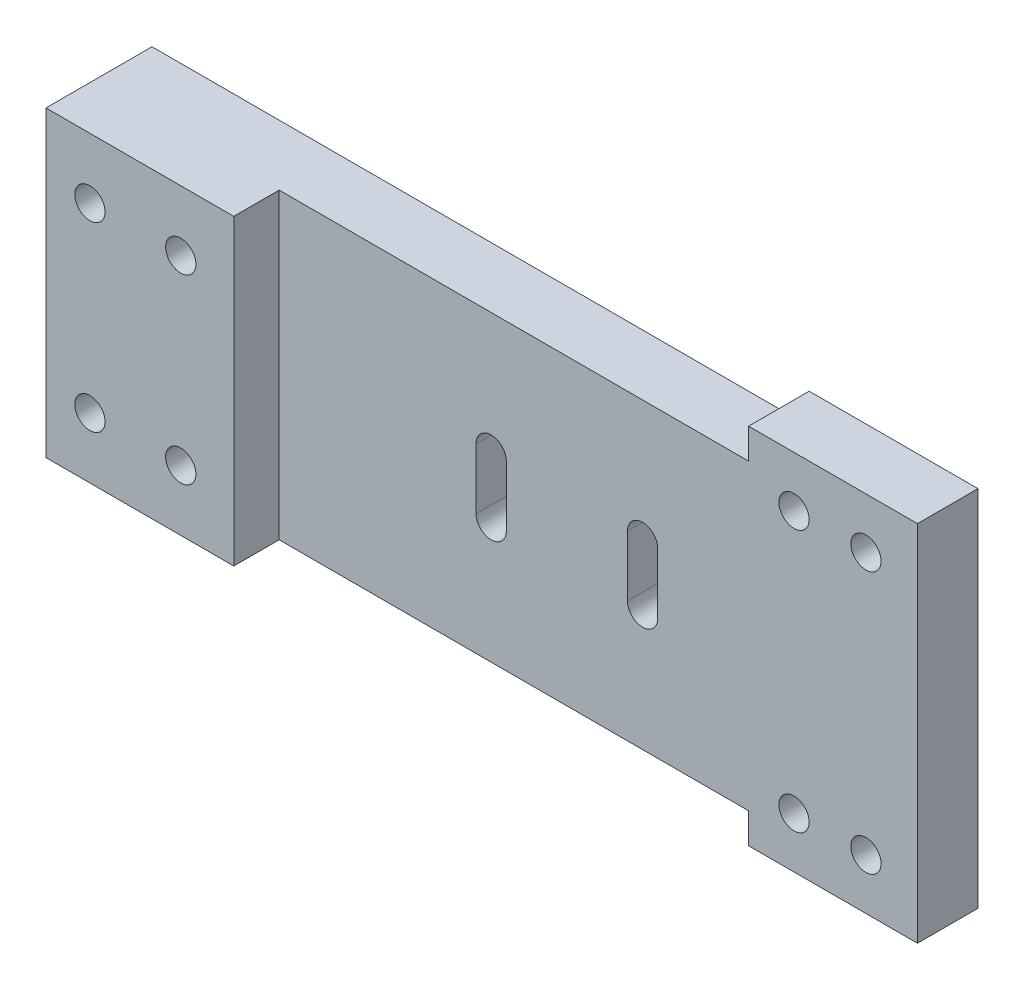
SolidWorks part; units mm, degrees
ref_plane "Front Plane" through (0, 0, 0) normal (0, 0, 1) x (1, 0, 0)
ref_plane "Top Plane" through (0, 0, 0) normal (0, 1, 0) x (1, 0, 0)
ref_plane "Right Plane" through (0, 0, 0) normal (1, 0, 0) x (0, 0, -1)
ref_plane "Plane1" through (0, 0, 246) normal (0, 0, 1) x (1, 0, 0)
sketch "Sketch1" plane through (0, 0, 246) normal (0, 0, 1) x (1, 0, 0)
  line L0 (227.2, 280) -> (336.3, 280)
  line L1 (336.3, 280) -> (336.3, 320)
  line L2 (336.3, 320) -> (227.2, 320)
  line L3 (227.2, 320) -> (227.2, 280)
  line L4 (282, 296) -> (282, 304)
  line L5 (278, 304) -> (278, 296)
  line L6 (302, 296) -> (302, 304)
  line L7 (298, 304) -> (298, 296)
  arc A0 (282, 304) -> (278, 304) centre (280, 304) ccw
  arc A1 (278, 296) -> (282, 296) centre (280, 296) ccw
  arc A2 (302, 304) -> (298, 304) centre (300, 304) ccw
  arc A3 (298, 296) -> (302, 296) centre (300, 296) ccw
extrude "Boss-Extrude1" add sketch "Sketch1" along normal blind 8
sketch "Sketch2" plane through (0, 0, 246) normal (0, 0, 1) x (1, 0, 0)
  line L0 (314, 276) -> (336.3, 276)
  line L1 (336.3, 276) -> (336.3, 324)
  line L2 (336.3, 324) -> (314, 324)
  line L3 (314, 324) -> (314, 276)
extrude "Boss-Extrude2" add sketch "Sketch2" along normal blind 8
ref_plane "Plane2" through (0, 0, 254) normal (0, 0, 1) x (1, 0, 0)
sketch "Sketch3" plane through (0, 0, 254) normal (0, 0, 1) x (1, 0, 0)
  line L0 (227.2, 280) -> (252, 280)
  line L1 (252, 280) -> (252, 320)
  line L2 (252, 320) -> (227.2, 320)
  line L3 (227.2, 320) -> (227.2, 280)
extrude "Boss-Extrude3" add sketch "Sketch3" along normal blind 6
ref_plane "Plane3" through (0, 0, 253.3) normal (0, 0, 1) x (1, 0, 0)
sketch "Sketch4" plane through (0, 0, 253.3) normal (0, 0, 1) x (1, 0, 0)
  circle A0 centre (233, 288) radius 2
  circle A1 centre (233, 312) radius 2
  circle A2 centre (245, 288) radius 2
  circle A3 centre (245, 312) radius 2
extrude "Cut-Extrude1" cut sketch "Sketch4" along normal blind 6.7
ref_plane "Plane4" through (0, 0, 247.3) normal (0, 0, 1) x (1, 0, 0)
sketch "Sketch5" plane through (0, 0, 247.3) normal (0, 0, 1) x (1, 0, 0)
  circle A0 centre (320, 282.7) radius 2
  circle A1 centre (320, 317.3) radius 2
  circle A2 centre (329.5, 282.7) radius 2
  circle A3 centre (329.5, 317.3) radius 2
extrude "Cut-Extrude2" cut sketch "Sketch5" along normal blind 6.7
sketch "Sketch6" plane through (0, 0, 246) normal (0, 0, 1) x (1, 0, 0)
  circle A0 centre (238, 294) radius 2
  circle A1 centre (238, 306) radius 2
  circle A2 centre (326, 292) radius 2
  circle A3 centre (326, 308) radius 2
extrude "Cut-Extrude3" cut sketch "Sketch6" along normal blind 6.7
ref_plane "Plane5" through (0, 300, 0) normal (0, 1, 0) x (1, 0, 0)
ref_plane "Plane6" through (0, 0, 300) normal (0, 0, 1) x (1, 0, 0)
ref_axis "ABAD_AXIS" through (341.755, 300, 300) along (-1, 0, 0)
